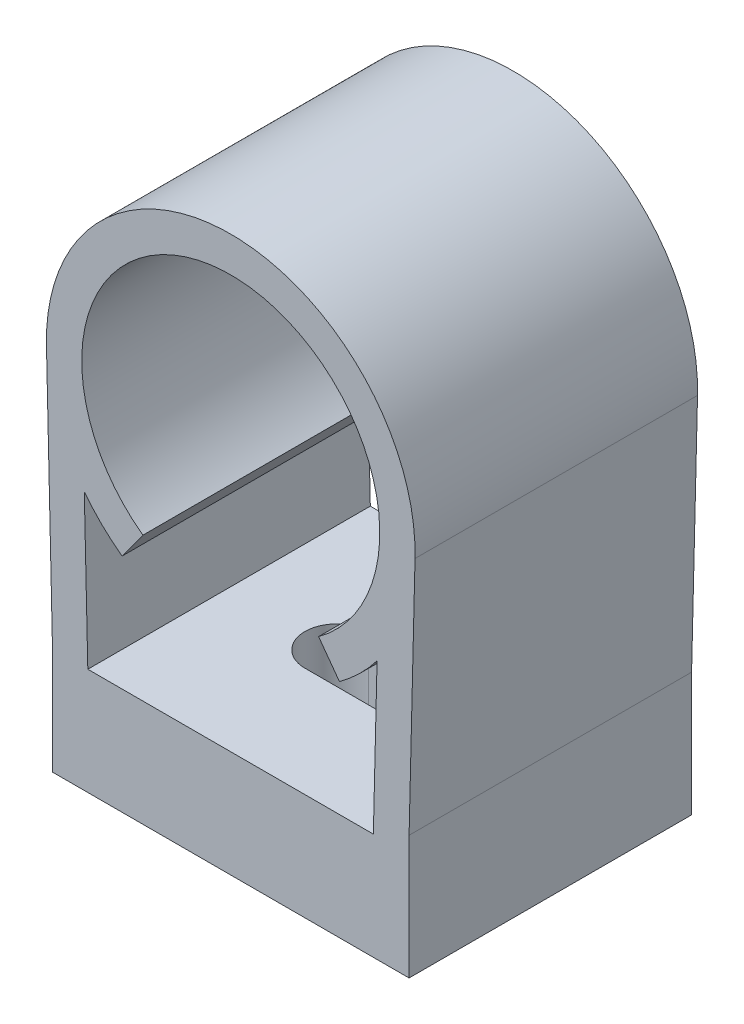
SolidWorks part; units mm, degrees
ref_plane "Front Plane" through (0, 0, 0) normal (0, 0, 1) x (1, 0, 0)
ref_plane "Top Plane" through (0, 0, 0) normal (0, 1, 0) x (1, 0, 0)
ref_plane "Right Plane" through (0, 0, 0) normal (1, 0, 0) x (0, 0, -1)
sketch "Sketch1" plane through (0, 0, 0) normal (0, 0, 1) x (1, 0, 0)
  line L0 (12.827, 0) -> (12.827, 26.67) construction
  line L1 (0, 0) -> (25.654, 0)
  line L2 (0, 0) -> (0, 7.874)
  line L3 (2.5452, 7.6792) -> (23.0836, 7.6792)
  line L4 (25.654, 0) -> (25.654, 8.89)
  line L5 (0, 7.874) -> (-0.4282, 26.363)
  line L6 (25.654, 8.89) -> (26.0818, 26.3451)
  line L7 (2.5452, 7.6792) -> (2.2918, 18.6198)
  line L8 (23.0836, 7.6792) -> (23.3514, 18.6057)
  line L10 (5.0096, 15.961) -> (6.5072, 18.0125)
  line L11 (20.6444, 15.961) -> (19.1468, 18.0125)
  arc A0 (19.1468, 18.0125) -> (6.5072, 18.0125) centre (12.827, 26.67) ccw
  arc A1 (26.0818, 26.3451) -> (-0.4282, 26.363) centre (12.827, 26.67) ccw
  arc A2 (2.2918, 18.6198) -> (5.0096, 15.961) centre (12.827, 26.67) ccw
  arc A3 (20.6444, 15.961) -> (23.3514, 18.6057) centre (12.827, 26.67) ccw
  point P17 (12.827, 15.9512)
  dimension "D2" = 21.4376
  dimension "D5" = 2.54
  dimension "D1" = 26.67
  dimension "D3" = 7.874
  dimension "D4" = 25.654
  dimension "D6" = 2.54
  dimension "D7" = 2.54
  dimension "D8" = 20.5384
  dimension "D9" = 1.404
extrude "Boss-Extrude1" add sketch "Sketch1" along normal blind 20.32
sketch "Sketch2" plane through (0, 0, 0) normal (0, -1, 0) x (1, 0, 0)
  line L0 (0, 20.32) -> (25.654, 0) construction
  line L1 (10.287, 10.16) -> (15.367, 10.16) construction
  line L2 (10.287, 12.446) -> (15.367, 12.446)
  line L3 (10.287, 7.874) -> (15.367, 7.874)
  arc A0 (10.287, 12.446) -> (10.287, 7.874) centre (10.287, 10.16) ccw
  arc A1 (15.367, 7.874) -> (15.367, 12.446) centre (15.367, 10.16) ccw
  point P6 (12.827, 10.16)
  dimension "D2" = 2.286
  dimension "D1" = 5.08
extrude "Cut-Extrude1" cut sketch "Sketch2" against normal up to next
